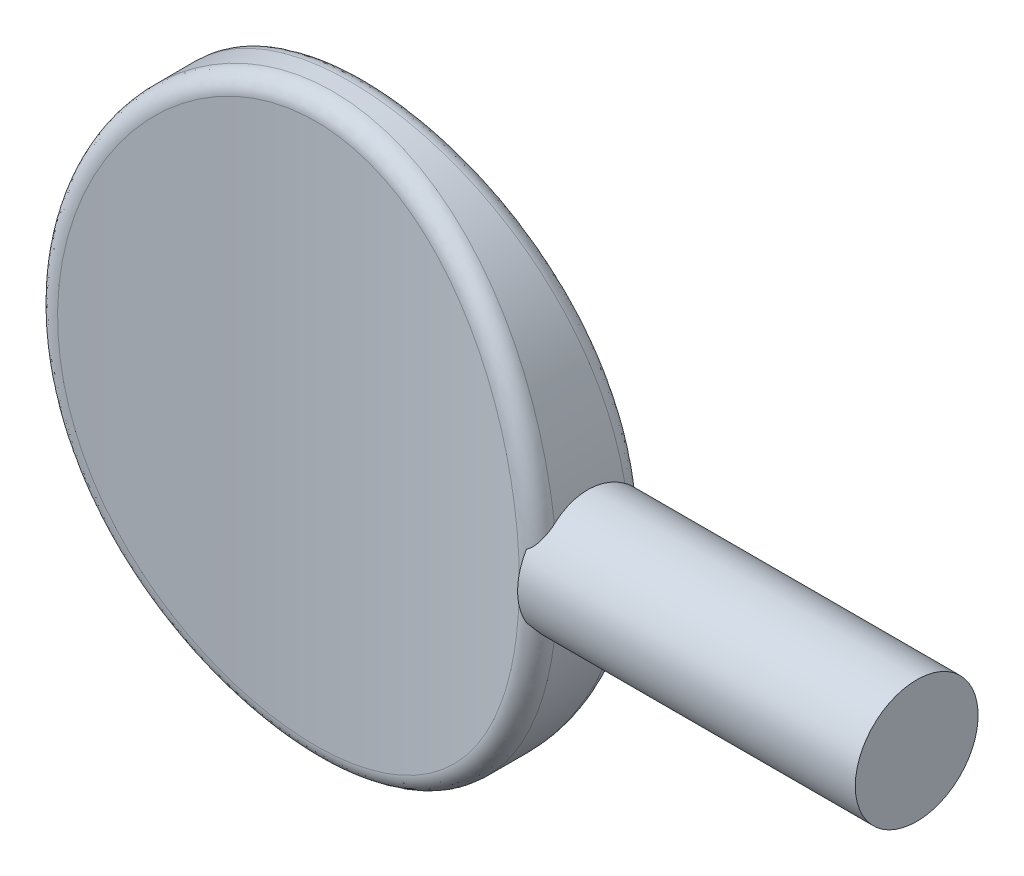
SolidWorks part; units mm, degrees
ref_plane "Front" through (0, 0, 0) normal (0, 0, 1) x (1, 0, 0)
ref_plane "Top" through (0, 0, 0) normal (0, 1, 0) x (1, 0, 0)
ref_plane "Right" through (0, 0, 0) normal (1, 0, 0) x (0, 0, -1)
ref_axis "Axis1" through (-50, 0, 0) along (1, 0, 0)
sketch "Sketch1" plane through (0, 0, 0) normal (0, 0, 1) x (1, 0, 0)
  line L0 (0, 0) -> (22.606, 0) construction
  line L1 (13.208, -2.413) -> (13.208, 2.413)
  line L2 (13.208, -2.413) -> (9.6776, -2.413) construction
  ellipse E0 centre (0, 0) end of major axis (0, -11.303) minor radius 9.906
  dimension "D2" = 3.302
  dimension "B" = 19.812
  dimension "L" = 12.7
extrude "Extrude1" add sketch "Sketch1" along normal mid plane 4.572
sketch "Sketch2" plane through (0, 0, 0) normal (0, 1, 0) x (1, 0, 0)
  line L0 (9.906, 2.286) -> (-9.906, 2.286) construction
  line L1 (0, 0) -> (0, 1.1721) construction
  line L2 (-1.7991, 0) -> (2.0444, 0) construction
  line L3 (-9.906, -2.286) -> (9.906, -2.286) construction
  line L6 (-9.906, 2.286) -> (-9.906, -2.286)
  line L7 (9.906, 2.286) -> (9.906, -2.286)
  arc A0 (-9.906, 2.286) -> (9.906, 2.286) centre (0, 40.2844) ccw
  arc A1 (-9.906, -2.286) -> (9.906, -2.286) centre (0, -40.2844) cw
extrude "Cut-Extrude1" cut sketch "Sketch2" against normal through all and the other way through all flip side to cut
fillet "Fillet3" radius 0.6773 2 edges at (-9.9037, -0.2444, 2.2854) (0.1692, 11.3014, -1.0164)
sketch "Sketch3" plane through (0, 0, 0) normal (0, 1, 0) x (1, 0, 0)
  line L1 (0, 0) -> (21.0288, 0) construction
  line L2 (0, 0) -> (22.606, 0) construction
  line L3 (13.208, 2.413) -> (13.208, 0) construction
  line L4 (13.208, 2.413) -> (22.606, 2.413)
  line L5 (22.606, 2.413) -> (22.606, 0)
  line L6 (13.208, 2.413) -> (9.3367, 2.413)
  line L7 (9.0722, 2.0783) -> (9.0722, 0)
  line L8 (9.3367, 0) -> (9.3367, 2.413) construction
  line L9 (9.0722, 0) -> (22.606, 0)
  arc A0 (9.3367, 2.413) -> (9.0722, 2.0783) centre (8.9927, 2.413) cw
  arc A3 (-9.906, 2.286) -> (9.906, 2.286) centre (0, 40.2844) ccw construction
revolve "Revolve1" add sketch "Sketch3" angle 360 about L0
cosmetic thread "Cosmetic Thread1" [suppressed]
sketch "Sketch4" plane through (0, 0, 0) normal (0, 0, 1) x (1, 0, 0)
  line L0 (0, 0) -> (27.7993, 0) construction
  line L1 (22.4227, 2.413) -> (22.606, 2.0955)
  line L2 (22.606, 2.0955) -> (22.7893, 2.413)
  line L3 (22.7893, 2.413) -> (22.7893, 2.7796)
  line L4 (22.7893, 2.7796) -> (22.4227, 2.7796)
  line L5 (22.4227, 2.7796) -> (22.4227, 2.413)
  dimension "D1" = 4.191
  dimension "D2" = 4.826
revolve "Cut-Revolve10" [suppressed] cut sketch "Sketch4" angle 360 about L0
pattern_linear "LPattern10" [suppressed] count 25 along (-1, 0, 0) of bodies 109
equation "\"D2@Sketch1\" = \"B@Sketch1\" / 6"
equation "\"D1@Fillet3\" = \"C1@Sketch2\" / 3"
equation "\"DIA@Sketch3\" = \"D@Sketch1\""
equation "\"D1@Cosmetic Thread1\" = \"L@Sketch1\""
equation "\"D1@Sketch4\" = \"D2@Cosmetic Thread1\""
equation "\"D2@Sketch4\" = \"DIA@Sketch3\""
equation "\"D1@LPattern10\" = \"D1@Cosmetic Thread1\" / \"P@LPattern10\" "
